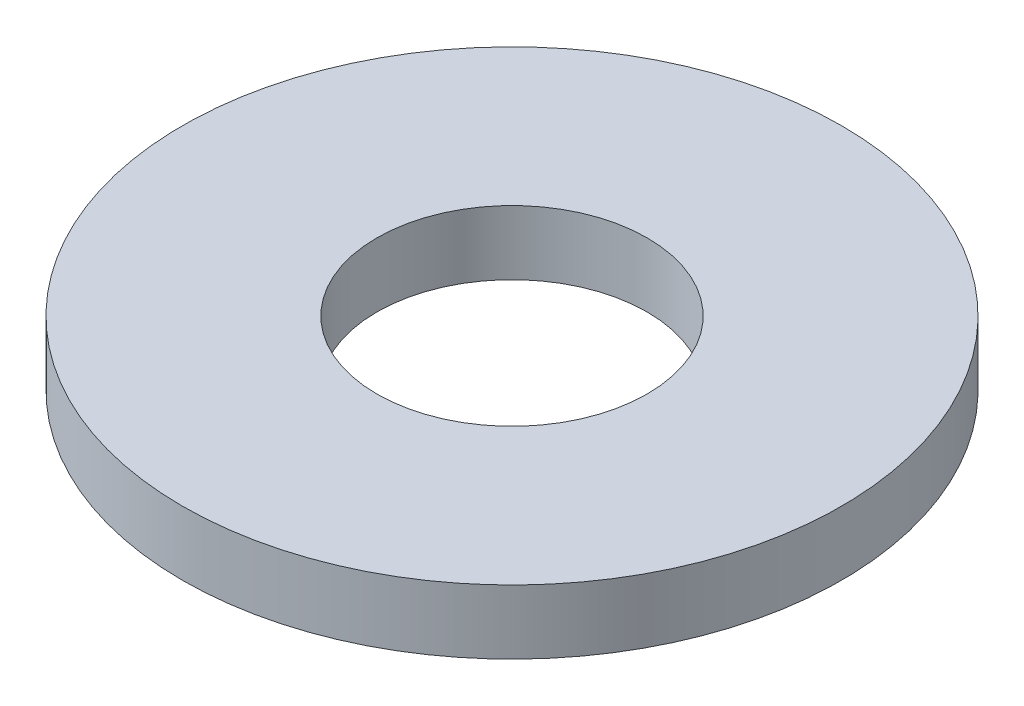
SolidWorks part; units mm, degrees
ref_plane "Front Plane" through (0, 0, 0) normal (0, 0, 1) x (1, 0, 0)
ref_plane "Top Plane" through (0, 0, 0) normal (0, 1, 0) x (1, 0, 0)
ref_plane "Right Plane" through (0, 0, 0) normal (1, 0, 0) x (0, 0, -1)
sketch "Sketch1" plane through (0, 0, 0) normal (0, 1, 0) x (1, 0, 0)
  circle A0 centre (0, 0) radius 97.5
  dimension "FLANGE_OD" = 195
extrude "Boss-Extrude1" add sketch "Sketch1" along normal blind 19
sketch "Sketch2" plane through (0, 0, 0) normal (0, 1, 0) x (1, 0, 0)
  circle A0 centre (0, 0) radius 40
  dimension "BORE_D" = 80
extrude "Cut-Extrude1" cut sketch "Sketch2" along normal through all
sketch "Sketch3" plane through (0, 19, 0) normal (0, 1, 0) x (1, 0, 0)
  circle A0 centre (0, 0) radius 36.0062 construction
  circle A1 centre (-36.0062, 0) radius 3.9029
  dimension "BOLT_D" = 7.8057
  dimension "BOLT_PCD" = 72.0124
extrude "Cut-Extrude2" cut sketch "Sketch3" against normal blind 12.7674 rebuild error yes
pattern_circular "CirPattern1" count 6 over 360 rebuild error yes
